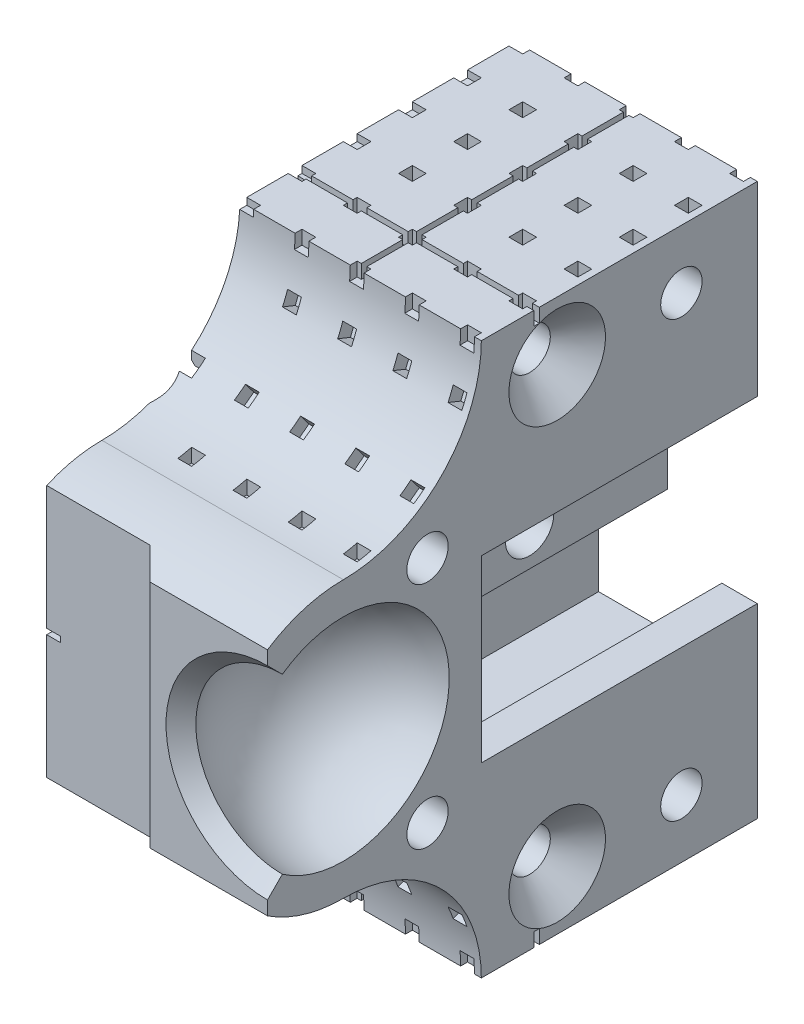
SolidWorks part; units mm, degrees
ref_plane "Front Plane" through (0, 0, 0) normal (0, 0, 1) x (1, 0, 0)
ref_plane "Top Plane" through (0, 0, 0) normal (0, 1, 0) x (1, 0, 0)
ref_plane "Right Plane" through (0, 0, 0) normal (1, 0, 0) x (0, 0, -1)
sketch "Sketch1" plane through (0, 0, 0) normal (0, 0, 1) x (1, 0, 0)
  line L0 (-11, -4.5) -> (-11, 9)
  line L2 (-11, 9) -> (-28.5, 9)
  line L3 (-28.5, 9) -> (-28.5, -11)
  line L13 (-22.5, 0.5) -> (-13.5, 0.5)
  line L14 (-13.5, 0.5) -> (-13.5, -1.8)
  line L19 (-11, -4.5) -> (-11, -17.5) construction
  line L20 (-16.5, -11) -> (-11, -11) construction
  line L21 (-16.5, -14) -> (-16.5, -8) construction
  line L22 (-28.5, -11) -> (-17.5, -11)
  line L23 (-16.5, -11) -> (-17.5, -11) construction
  line L24 (-22.5, -8.5) -> (-20.2, -8.5)
  line L25 (-20.2, -8.5) -> (-18.8591, -7.1591)
  line L26 (-18.8591, -7.1591) -> (-17.5, -8.4332)
  line L27 (-17.5, -8.4332) -> (-17.5, -11)
  line L29 (-22.5, 0.5) -> (-22.5, -8.5)
  line L30 (-22, -8) -> (-22, 0) construction
  line L31 (-13.5, -1.8) -> (-14.8409, -3.1409)
  line L32 (-14.8409, -3.1409) -> (-13.5668, -4.5)
  line L33 (-13.5668, -4.5) -> (-11, -4.5)
  line L34 (-16.5, -8) -> (-19.7, -5) construction
  line L35 (-17, -2.3) -> (-14, -5.5) construction
  line L36 (-14, -5.5) -> (-8, -5.5) construction
  line L37 (-20.7, -8) -> (-22, -8) construction
  line L38 (-14, 0) -> (-14, -1.3) construction
  line L39 (-20.7, -8) -> (-20.2, -8.5) construction
  line L40 (-14, -1.3) -> (-13.5, -1.8) construction
  line L41 (-22, 0) -> (-14, 0) construction
  point P41 (-22, -4)
  point P45 (-11, -5.5)
  dimension "D1" = 1
  dimension "D2" = 1
  dimension "D3" = 1
  dimension "D4" = 1
  dimension "D5" = 0.5
  dimension "D6" = 0.5
  dimension "D7" = 0.5
  dimension "D8" = 0.5
  dimension "D9" = 6
  dimension "D10" = 8.5
extrude "Boss-Extrude1" add sketch "Sketch1" against normal blind 20
mirror "Mirror1" about plane through (-28.5, -11, -20) normal (0, -1, 0) of bodies 101
sketch "Sketch2" plane through (0, 0, 0) normal (0, 0, 1) x (1, 0, 0)
  line L1 (-11, 9) -> (-28.5, 9)
  line L2 (-11, 9) -> (-11, -31)
  line L3 (-11, -31) -> (-28.5, -31)
  line L4 (-28.5, 9) -> (-28.5, -31)
extrude "Boss-Extrude2" add sketch "Sketch2" along normal blind 20
sketch "Sketch3" plane through (-11, 0, 0) normal (1, 0, 0) x (0, 0, -1)
  line L0 (20, 9) -> (-20, 9) construction
  line L1 (20, -31) -> (-20, -31) construction
  line L2 (-20, -31) -> (-20, 9) construction
  line L3 (0, 9) -> (0, -31) construction
  line L4 (-10, -1) -> (-10, -21) construction
  line L5 (-15.5, -2.6484) -> (-15.5, -19.3516)
  line L6 (0, 9) -> (-20, 9)
  line L7 (-20, 9) -> (-20, -31)
  line L8 (-20, -31) -> (0, -31)
  arc A0 (-10, -1) -> (-15.5, -2.6484) centre (-10, -11) ccw
  arc A1 (0, 9) -> (-10, -1) centre (-10, 9) cw
  arc A2 (-10, -21) -> (0, -31) centre (-10, -31) cw
  arc A3 (-15.5, -19.3516) -> (-10, -21) centre (-10, -11) ccw
  arc A4 (-15.5, -2.6484) -> (-15.5, -19.3516) centre (-10, -11) ccw construction
  dimension "D1" = 10
  dimension "D2" = 4.5
extrude "Cut-Extrude1" cut sketch "Sketch3" against normal through all
sketch "Sketch4" plane through (-11, 0, 0) normal (1, 0, 0) x (0, 0, -1)
  line L0 (-10, -1) -> (-10, -21) construction
  circle A0 centre (-10, -11) radius 7.675
  dimension "D1" = 15.35
revolve "Cut-Revolve2" cut sketch "Sketch4" angle 360 about L0 region at (-11, -11, 6.7426)
chamfer "Chamfer1" distance 2 angle 45 1 edges at (-16.3531, -11, 15.5) first distance on face at (-17.7255, -11, 15.5)
sketch "Sketch5" plane through (-11, 0, 0) normal (1, 0, 0) x (0, 0, -1)
  line L0 (14.5, 4.75) -> (5.5, 4.75) construction
  line L1 (20, 4.75) -> (14.5, 4.75) construction
  line L2 (20, -4.5) -> (20, 9) construction
  line L4 (20, 0.5) -> (20, 9) construction
  line L5 (0, 9) -> (0, 4.75) construction
  line L6 (5.5, 4.75) -> (0, 4.75) construction
  line L7 (-3.9005, -2.6873) -> (-3.0904, -7.6589) construction
  line L8 (-3.0904, -7.6589) -> (-8.611, -0.9031) construction
  line L9 (0, 0.5) -> (-3.9005, -2.6873) construction
  line L10 (-3.9005, -2.6873) -> (-8.611, -0.9031) construction
  line L11 (-8.611, -0.9031) -> (0, 0.5) construction
  line L12 (0, 0.5) -> (-3.0904, -7.6589) construction
  circle A0 centre (5.5, 4.75) radius 1.5
  circle A1 centre (14.5, 4.75) radius 1.5
  circle A2 centre (-3.9005, -2.6873) radius 1.5
  arc A3 (-14.4208, -17.2739) -> (-14.4208, -4.7261) centre (-10, -11) ccw construction
  arc A4 (-10, -1) -> (0, 9) centre (-10, 9) ccw construction
  point P5 (20, 0.5)
  dimension "D1" = 9
  dimension "D2" = 3
extrude "Cut-Extrude2" cut sketch "Sketch5" against normal through all
ref_plane "Plane1" through (0, -11, 0) normal (0, 1, 0) x (1, 0, 0)
chamfer "Chamfer2" distance 2 angle 45 4 edges at (-11, 6.25, -5.5) (-28.5, 6.25, -5.5) (-28.5, -1.1873, 3.9005) (-28.5, 6.25, -14.5)
sketch "Sketch11" plane through (-28.5, 0, 0) normal (-1, 0, 0) x (0, 0, 1)
  line L0 (-10, 9) -> (-10, -31) construction
  line L1 (-20, 9) -> (0, 9) construction
  line L2 (-20, -31) -> (0, -31) construction
  circle A0 centre (-10, -11) radius 1.75
  dimension "D1" = 3.5
extrude "Cut-Extrude7" cut sketch "Sketch11" against normal through all
sketch "Sketch6" plane through (-28.5, 0, 0) normal (-1, 0, 0) x (0, 0, 1)
  line L0 (-16.2321, 7.75) -> (-12.7679, 7.75)
  line L1 (-12.7679, 7.75) -> (-11.0359, 4.75)
  line L2 (-11.0359, 4.75) -> (-12.7679, 1.75)
  line L3 (-12.7679, 1.75) -> (-16.2321, 1.75)
  line L4 (-16.2321, 1.75) -> (-17.9641, 4.75)
  line L5 (-17.9641, 4.75) -> (-16.2321, 7.75)
  circle A0 centre (-14.5, 4.75) radius 3.4641 construction
  point P5 (-5.5, 4.75)
  dimension "D1" = 6
extrude "Cut-Extrude3" cut sketch "Sketch6" against normal blind 3
pattern_sketch "Sketch-Pattern1" of "Cut-Extrude3" driven by "Sketch6"
sketch "Sketch10" plane through (-28.5, 0, 0) normal (-1, 0, 0) x (0, 0, 1)
  line L0 (3.9005, 0.7768) -> (6.9005, -0.9553)
  line L1 (6.9005, -0.9553) -> (6.9005, -4.4194)
  line L2 (6.9005, -4.4194) -> (3.9005, -6.1514)
  line L3 (3.9005, -6.1514) -> (0.9005, -4.4194)
  line L4 (0.9005, -4.4194) -> (0.9005, -0.9553)
  line L5 (0.9005, -0.9553) -> (3.9005, 0.7768)
  circle A0 centre (3.9005, -2.6873) radius 3.4641 construction
  dimension "D1" = 6
extrude "Cut-Extrude6" cut sketch "Sketch10" against normal blind 3
mirror "Mirror2" about plane through (0, -11, 0) normal (0, 1, 0) of "Chamfer2", "Cut-Extrude2"
mirror "Mirror3" about plane through (0, -11, 0) normal (0, 1, 0) of "Cut-Extrude6", "Cut-Extrude2", "Cut-Extrude3", "Sketch-Pattern1"
sketch "Sketch7" plane through (0, -11, 0) normal (0, 1, 0) x (1, 0, 0)
  line L0 (-28.5, -14) -> (-21, -14)
  line L1 (-21, -14) -> (-11, -24)
  line L2 (-11, -24) -> (-28.5, -24)
  line L3 (-28.5, -24) -> (-28.5, -14)
  line L4 (-28.5, 9) -> (-28.5, 2) construction
  line L5 (-28.5, -15.5) -> (-11, -15.5) construction
  dimension "D1" = 7.5
  dimension "D2" = 1.5
  dimension "D3" = 135
  dimension "D4" = 10
extrude "Cut-Extrude4" cut sketch "Sketch7" against normal mid plane 23
fillet "Fillet1" [suppressed] radius 3
sketch "Sketch9" [suppressed] plane through (-17.5, 0, 17.5) normal (-0.7071, 0, 0.7071) x (0.7071, 0, 0.7071)
  line L0 (-2.8284, -11) -> (-1.3284, -11) construction
  line L1 (-2.8284, -4.8694) -> (-2.8284, -17.1306) construction
  line L2 (-1.3284, -16.5) -> (-1.3284, -5.5) construction
  ellipse E0 centre (-1.3284, -11) end of major axis (-1.3284, -5.5) minor radius 3.75
  dimension "D1" = 7.5
  dimension "D2" = 11
  dimension "D3" = 1.5
extrude "Cut-Extrude5" [suppressed] cut sketch "Sketch9" against normal through all
sketch "Sketch12" plane through (-28.5, 0, 0) normal (-1, 0, 0) x (0, 0, 1)
  line L12 (-0.5, -11.5) -> (0.5, -10.5) construction
  line L13 (14, -11) -> (0, -11) construction
  line L14 (14, -20.1652) -> (14, -1.8348) construction
  line L15 (0, -11) -> (0, 0) construction
  line L17 (0.5, -10.5) -> (-0.5, -10.5)
  line L18 (0.5, -10.5) -> (0.5, -11.5)
  line L19 (0.5, -11.5) -> (-0.5, -11.5)
  line L20 (-0.5, -10.5) -> (-0.5, -11.5)
  point P21 (0, -11)
  dimension "D1" = 1
extrude "Cut-Extrude8" cut sketch "Sketch12" against normal blind 1
pattern_linear "LPattern1" count 6 spacing 4 along (0, 0, -1) count 4 spacing 4 along (0, 0, 1) of "Cut-Extrude8" pattern seed only yes
pattern_linear "LPattern2" count 6 spacing 4 along (0, -1, 0) count 6 spacing 4 along (0, 1, 0) of "LPattern1" pattern seed only yes
sketch "Sketch13" plane through (-28.5, 0, 0) normal (-1, 0, 0) x (0, 0, 1)
  line L0 (-19.5, -11.5) -> (-19.5, -10.5) construction
  line L1 (-19.5, -10.8) -> (-4.2, -10.8)
  line L2 (-19.5, -10.8) -> (-19.5, -11.2)
  line L3 (-19.5, -11.2) -> (-4.2, -11.2)
  line L4 (14, -10.8) -> (14, -11.2)
  line L5 (14, -20.1652) -> (14, -1.8348) construction
  line L6 (-4.5, 0.5) -> (-3.5, 0.5) construction
  line L7 (-4.2, 0.5) -> (-3.8, 0.5)
  line L8 (-4.2, 0.5) -> (-4.2, -10.8)
  line L9 (-4.2, -22.5) -> (-3.8, -22.5)
  line L10 (-3.8, 0.5) -> (-3.8, -10.8)
  line L11 (-3.5, -22.5) -> (-4.5, -22.5) construction
  line L12 (-3.8, -11.2) -> (-3.8, -22.5)
  line L13 (-3.8, -10.8) -> (-3.8, -11.2) construction
  line L14 (-3.8, -10.8) -> (14, -10.8)
  line L15 (-4.2, -10.8) -> (-3.8, -10.8) construction
  line L16 (-4.2, -11.2) -> (-4.2, -22.5)
  line L17 (-4.2, -10.8) -> (-4.2, -11.2) construction
  line L18 (-3.8, -11.2) -> (14, -11.2)
  line L19 (-4.2, -11.2) -> (-3.8, -11.2) construction
  point P8 (14, -11)
  point P17 (-4, -22.5)
  dimension "D1" = 0.4
extrude "Cut-Extrude9" cut sketch "Sketch13" against normal blind 1
sketch "Sketch14" plane through (0, -31, 0) normal (0, -1, 0) x (1, 0, 0)
  line L0 (-27.5, -3.5) -> (-27.5, -4.5) construction
  line L5 (-24.5, -0.5) -> (-23.5, -0.5)
  line L6 (-24.5, -0.5) -> (-24.5, 0.5)
  line L7 (-24.5, 0.5) -> (-23.5, 0.5)
  line L8 (-23.5, -0.5) -> (-23.5, 0.5)
  line L9 (-27.5, -0.5) -> (-24.5, -0.5) construction
  line L10 (-27.5, -3.5) -> (-27.5, -0.5) construction
  line L11 (-24.5, -0.5) -> (-24.5, -3.5) construction
  line L12 (-24.5, -4.5) -> (-23.5, -4.5)
  line L13 (-24.5, -4.5) -> (-24.5, -3.5)
  line L14 (-24.5, -3.5) -> (-23.5, -3.5)
  line L15 (-23.5, -4.5) -> (-23.5, -3.5)
extrude "Cut-Extrude10" cut sketch "Sketch14" against normal blind 1
pattern_linear "LPattern3" count 5 spacing 4 along (0, 0, -1) count 4 spacing 4 along (1, 0, 0) of "Cut-Extrude10"
sketch "Sketch15" plane through (0, -31, 0) normal (0, -1, 0) x (1, 0, 0)
  line L0 (-11, -20) -> (-11, 0) construction
  line L1 (-28.5, -4.2) -> (-20.2, -4.2)
  line L2 (-28.5, -4.2) -> (-28.5, -3.8)
  line L3 (-28.5, -3.8) -> (-20.2, -3.8)
  line L4 (-11, -4.2) -> (-11, -3.8)
  line L5 (-28.5, -3.5) -> (-28.5, -4.5) construction
  line L6 (-20.2, -19.9499) -> (-19.8, -19.9499)
  line L7 (-20.2, -19.9499) -> (-20.2, -4.2)
  line L8 (-20.2, 0.0501) -> (-19.8, 0.0501)
  line L9 (-19.8, -19.9499) -> (-19.8, -4.2)
  line L10 (-20.5, 0.0501) -> (-19.5, 0.0501) construction
  line L11 (-20.2, -3.8) -> (-20.2, 0.0501)
  line L12 (-20.2, -4.2) -> (-20.2, -3.8) construction
  line L13 (-19.8, -3.8) -> (-11, -3.8)
  line L14 (-20.2, -3.8) -> (-19.8, -3.8) construction
  line L15 (-19.8, -3.8) -> (-19.8, 0.0501)
  line L16 (-19.8, -4.2) -> (-19.8, -3.8) construction
  line L17 (-19.8, -4.2) -> (-11, -4.2)
  line L18 (-20.2, -4.2) -> (-19.8, -4.2) construction
  point P10 (-28.5, -4)
  point P13 (-20, 0.0501)
  dimension "D1" = 0.4
extrude "Cut-Extrude11" cut sketch "Sketch15" against normal blind 1
sketch "Sketch16" plane through (-28.5, 0, 0) normal (-1, 0, 0) x (0, 0, 1)
  line L0 (2.995, -22.5203) -> (3.7941, -21.9191)
  line L1 (2.995, -22.5203) -> (3.5962, -23.3194)
  line L2 (3.7941, -21.9191) -> (4.3953, -22.7183)
  line L3 (3.5962, -23.3194) -> (4.3953, -22.7183)
  line L4 (-0.0159, -26.4551) -> (-0.3873, -27.3836)
  line L5 (-0.0159, -26.4551) -> (0.9125, -26.8265)
  line L6 (-0.3873, -27.3836) -> (0.5412, -27.755)
  line L7 (0.9125, -26.8265) -> (0.5412, -27.755)
  line L8 (7.5, -20.3175) -> (8.5, -20.3175)
  line L9 (7.5, -20.3175) -> (7.5, -21.3175)
  line L10 (8.5, -20.3175) -> (8.5, -21.3175)
  line L11 (7.5, -21.3175) -> (8.5, -21.3175)
  line L12 (-0.5, -23.5) -> (0.5, -23.5) construction
  line L13 (-0.5, -27.5) -> (0.4935, -27.8974) construction
  line L14 (0.4935, -27.8974) -> (0.5412, -27.755) construction
  line L15 (0.5, -26.5) -> (0.9762, -26.6905) construction
  line L16 (0.9762, -26.6905) -> (0.9125, -26.8265) construction
  line L17 (3.5, -23.4007) -> (3.5962, -23.3194)
  line L18 (4.3953, -22.7183) -> (4.5, -22.6484)
  line L20 (7.5, -18.5) -> (7.5, -19.5) construction
  arc A0 (3.5, -23.4007) -> (0.0125, -30.5) centre (10, -31) ccw construction
  arc A2 (6.5316, -21.6208) -> (4.5, -22.6484) centre (10, -31) ccw construction
  arc A3 (10, -21) -> (6.5316, -21.6208) centre (10, -31) ccw construction
extrude "Cut-Extrude12" cut sketch "Sketch16" against normal blind 1 from surface contours L7 L5 L4 L6 | L1 L3 L2 L0 | L9 L11 L10 L8 region at (-28.5, -22.6193, 3.6952) region at (-28.5, -27.105, 0.2626) region at (-28.5, -20.8175, 8) starting at face at (-24.5, -30.4998, -0.2406)
mirror "Mirror4" about plane through (0, -11, 0) normal (0, 1, 0) of "LPattern3", "Cut-Extrude11", "Cut-Extrude10"
pattern_linear "LPattern6" count 4 spacing 4 along (1, 0, 0) of "Cut-Extrude12"
mirror "Mirror6" about plane through (0, -11, 0) normal (0, 1, 0) of "LPattern6"
